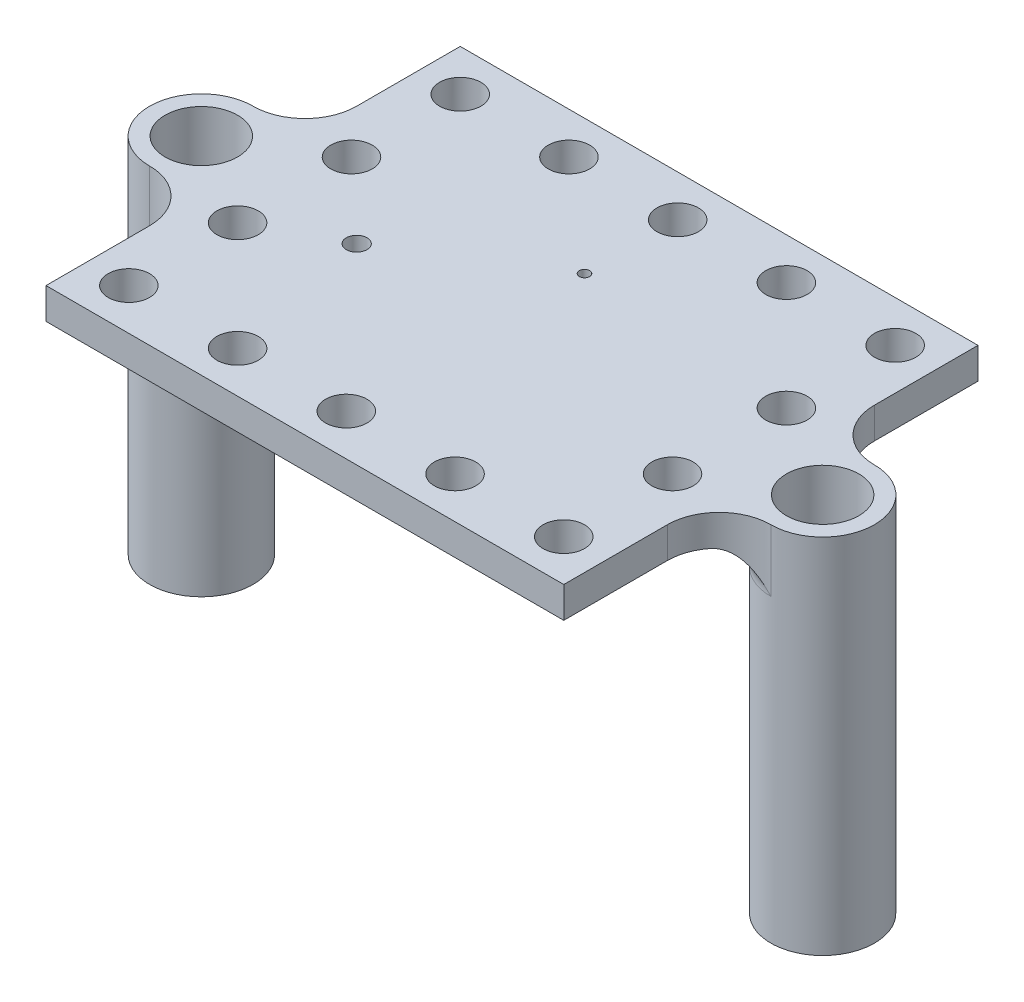
SolidWorks part; units mm, degrees
ref_plane "Plan de face" through (0, 0, 0) normal (0, 0, 1) x (1, 0, 0)
ref_plane "Plan de dessus" through (0, 0, 0) normal (0, 1, 0) x (1, 0, 0)
ref_plane "Plan de droite" through (0, 0, 0) normal (1, 0, 0) x (0, 0, -1)
sketch "Esquisse1" plane through (0, 0, 0) normal (0, 1, 0) x (1, 0, 0)
  line L1 (-25, -20) -> (25, -20)
  line L2 (-25, -20) -> (-25, 20)
  line L3 (-25, 20) -> (25, 20)
  line L4 (25, -20) -> (25, 20)
  line L5 (-25, -20) -> (25, 20) construction
  line L6 (-25, 20) -> (25, -20) construction
  point P0 (0, 0)
  dimension "D1" = 50
  dimension "D2" = 40
extrude "Boss.-Extru.1" add sketch "Esquisse1" along normal blind 3
sketch "Esquisse2" plane through (0, 3, 0) normal (0, 1, 0) x (1, 0, 0)
  line L0 (0, 0) -> (35, 0) construction
  line L1 (30, 5) -> (30, -5) construction
  line L2 (30, 5) -> (25, 5)
  line L3 (25, -20) -> (25, 20) construction
  line L4 (25, 5) -> (25, -5)
  line L5 (25, -5) -> (30, -5)
  arc A0 (30, 5) -> (30, -5) centre (30, 0) cw
  dimension "D1" = 5
  dimension "D2" = 5
extrude "Boss.-Extru.2" add sketch "Esquisse2" against normal up to surface (3 mm away) up to face at (0, 0, 0)
sketch "Esquisse4" plane through (0, 0, 0) normal (0, -1, 0) x (1, 0, 0)
  circle A0 centre (30, 0) radius 5
  arc A1 (30, -5) -> (30, 5) centre (30, 0) ccw construction
extrude "Boss.-Extru.3" add sketch "Esquisse4" along normal blind 32
sketch "Esquisse5" plane through (0, 3, 0) normal (0, 1, 0) x (1, 0, 0)
  circle A0 centre (30, 0) radius 3.5
  dimension "D1" = 7
extrude "Enlèv. mat.-Extru.1" cut sketch "Esquisse5" against normal blind 32
sketch "Esquisse6" plane through (0, -29, 0) normal (0, 1, 0) x (1, 0, 0)
  circle A0 centre (30, 0) radius 1.7
  dimension "D1" = 3.4
extrude "Enlèv. mat.-Extru.2" cut sketch "Esquisse6" against normal up to next
fillet "Congé1" radius 3 1 edges at (25, 0, 0)
mirror "Symétrie3" about plane through (0, 0, 0) normal (1, 0, 0) of "Congé1", "Enlèv. mat.-Extru.2", "Enlèv. mat.-Extru.1", "Boss.-Extru.3", "Boss.-Extru.2"
fillet "Congé2" radius 5 4 edges at (25, 1.4263, -5) (25, 1.4263, 5) (-25, 1.4263, -5) (-25, 1.4263, 5)
sketch "Esquisse7" plane through (0, 3, 0) normal (0, 1, 0) x (1, 0, 0)
  line L0 (0, 0) -> (0, 16) construction
  line L1 (25, 20) -> (-25, 20) construction
  circle A0 centre (0, 16) radius 2
  dimension "D1" = 4
  dimension "D2" = 4
extrude "Enlèv. mat.-Extru.3" cut sketch "Esquisse7" against normal up to next
pattern_linear "Répétition linéaire1" count 3 spacing 10.5 along (1, 0, 0) count 3 spacing 10.5 along (-1, 0, 0) of "Enlèv. mat.-Extru.3" pattern seed only yes
mirror "Symétrie4" about plane through (0, 0, 0) normal (0, 0, 1) of "Répétition linéaire1"
sketch "Esquisse8" plane through (0, 3, 0) normal (0, 1, 0) x (1, 0, 0)
  line L0 (-21, 5.5) -> (-21, -5.5) construction
  line L1 (-21, 0) -> (0, 0) construction
  line L2 (-21, 16) -> (-21, -16) construction
  circle A0 centre (-21, 5.5) radius 2
  circle A1 centre (-21, -5.5) radius 2
  dimension "D2" = 4
  dimension "D3" = 4
  dimension "D1" = 11
extrude "Enlèv. mat.-Extru.4" cut sketch "Esquisse8" against normal up to next
mirror "Symétrie5" about plane through (0, 0, 0) normal (1, 0, 0) of "Enlèv. mat.-Extru.4"
sketch "Esquisse9" plane through (0, 0, 0) normal (0, 1, 0) x (1, 0, 0)
  line L0 (0, 0) -> (0, 7) construction
  line L1 (-17, 12.5) -> (17, 12.5) construction
  line L2 (-17, 12.5) -> (-17, -12.5) construction
  line L3 (-17, -12.5) -> (17, -12.5) construction
  line L4 (17, 12.5) -> (17, -12.5) construction
  line L5 (-17, 12.5) -> (17, -12.5) construction
  line L6 (-17, -12.5) -> (17, 12.5) construction
  circle A0 centre (-13.5, -1.5) radius 3
  circle A1 centre (0, 7) radius 3
  point P0 (0, 0)
  dimension "D5" = 6
  dimension "D7" = 6
  dimension "D1" = 25
  dimension "D2" = 34
  dimension "D3" = 11
  dimension "D4" = 3.5
  dimension "D6" = 5.5
extrude "Boss.-Extru.4" add sketch "Esquisse9" against normal blind 5
sketch "Esquisse10" plane through (0, 3, 0) normal (0, 1, 0) x (1, 0, 0)
  circle A0 centre (-13.5, -1.5) radius 1
  circle A1 centre (0, 7) radius 0.5
  circle A2 centre (-13.5, -1.5) radius 3 construction
  circle A3 centre (0, 7) radius 3 construction
  dimension "D1" = 2
  dimension "D2" = 1
extrude "Enlèv. mat.-Extru.6" cut sketch "Esquisse10" against normal up to next
fillet "Congé3" radius 2 2 edges at (0, 0, -10) (-13.5, 0, -1.5)
